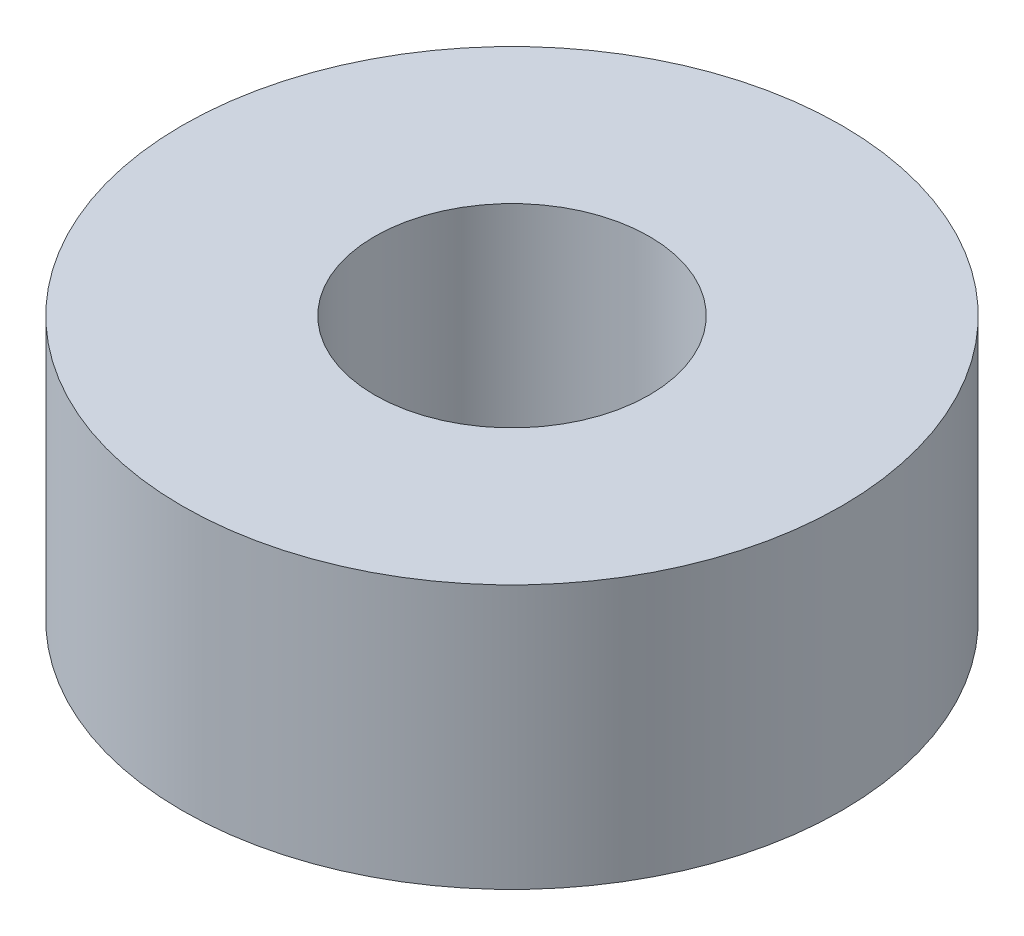
SolidWorks part; units mm, degrees
ref_plane "Front Plane" through (0, 0, 0) normal (0, 0, 1) x (1, 0, 0)
ref_plane "Top Plane" through (0, 0, 0) normal (0, 1, 0) x (1, 0, 0)
ref_plane "Right Plane" through (0, 0, 0) normal (1, 0, 0) x (0, 0, -1)
sketch "Sketch1" plane through (0, 0, 0) normal (0, 1, 0) x (1, 0, 0)
  circle A0 centre (0, 0) radius 30
  dimension "FLANGE_OD" = 60
extrude "Boss-Extrude1" add sketch "Sketch1" along normal blind 24
sketch "Sketch2" plane through (0, 0, 0) normal (0, 1, 0) x (1, 0, 0)
  circle A0 centre (0, 0) radius 12.5
  dimension "BORE_D" = 25
extrude "Cut-Extrude1" cut sketch "Sketch2" along normal through all
sketch "Sketch3" plane through (0, 24, 0) normal (0, 1, 0) x (1, 0, 0)
  circle A0 centre (0, 0) radius 8.3574 construction
  circle A1 centre (-8.3574, 0) radius 2.1866
  dimension "BOLT_D" = 4.3731
  dimension "BOLT_PCD" = 16.7148
extrude "Cut-Extrude2" cut sketch "Sketch3" against normal blind 17.2626 rebuild error yes
pattern_circular "CirPattern1" count 6 over 360 rebuild error yes
